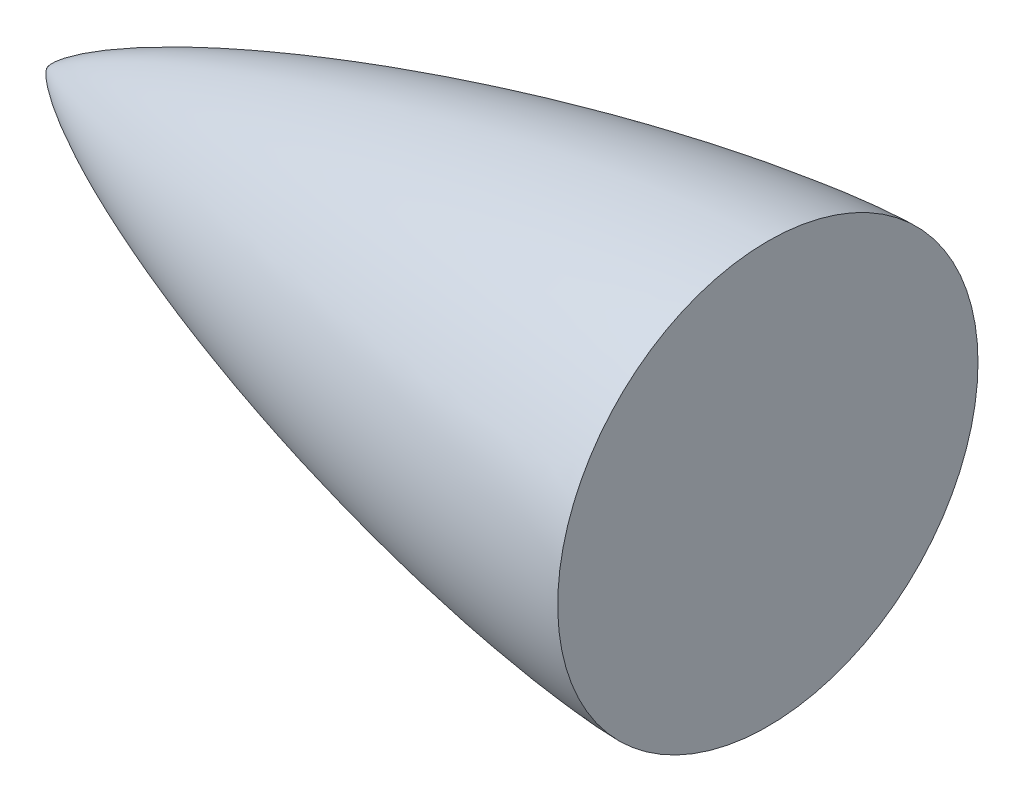
SolidWorks part; units mm, degrees
ref_plane "Front Plane" through (0, 0, 0) normal (0, 0, 1) x (1, 0, 0)
ref_plane "Top Plane" through (0, 0, 0) normal (0, 1, 0) x (1, 0, 0)
ref_plane "Right Plane" through (0, 0, 0) normal (1, 0, 0) x (0, 0, -1)
sketch "Sketch1" plane through (0, 0, 0) normal (0, 0, 1) x (1, 0, 0)
  line L0 (0, 0) -> (304.8, 0) construction
  line L1 (0, 0) -> (0, 88.9) construction
  line L2 (304.8, 88.9151) -> (304.8, 0)
  line L3 (304.8, 0) -> (0, 0)
  spline S0 degree 4 poles (0, 0) (0.0015, 0.0119) (0.0057, 0.0356) (0.0182, 0.0821) (0.05, 0.1729) (0.0937, 0.2728) (0.1482, 0.3816) (0.2338, 0.5371) (0.3732, 0.766) (0.6385, 1.1485) (1.1395, 1.7727) (2.0247, 2.7262) (3.5433, 4.142) (6.1054, 6.2185) (10.3073, 9.1835) (16.4637, 12.9823) (26.3502, 18.3873) (39.6719, 24.7722) (55.7804, 31.646) (74.2558, 38.7324) (92.9294, 45.2746) (111.76, 51.3489) (130.7203, 57.0039) (149.7928, 62.2678) (168.9648, 67.1561) (188.2278, 71.673) (207.5755, 75.8125) (227.0037, 79.5561) (246.5101, 82.8706) (263.6459, 85.3431) (278.3826, 87.091) (289.376, 88.1032) (296.0263, 88.5742) (300.7874, 88.8121) (303.0799, 88.8877) (304.2266, 88.912) (304.8, 88.9151) knots 0 0 0 0 0 0.00015 0.000299 0.000599 0.001198 0.001506 0.001815 0.002809 0.004534 0.0073 0.011775 0.018999 0.03037 0.048342 0.07578 0.109043 0.170642 0.232242 0.293841 0.35544 0.41704 0.478639 0.540238 0.601837 0.663437 0.725036 0.786635 0.848235 0.909834 0.940634 0.971433 0.985717 0.992858 1 1 1 1 1 construction
  spline S1 degree 4 poles (0, 0) (0.0015, 0.0119) (0.0057, 0.0356) (0.0182, 0.0821) (0.05, 0.1729) (0.0937, 0.2728) (0.1482, 0.3816) (0.2338, 0.5371) (0.3732, 0.766) (0.6385, 1.1485) (1.1395, 1.7727) (2.0247, 2.7262) (3.5433, 4.142) (6.1054, 6.2185) (10.3073, 9.1835) (16.4637, 12.9823) (26.3502, 18.3873) (39.6719, 24.7722) (55.7804, 31.646) (74.2558, 38.7324) (92.9294, 45.2746) (111.76, 51.3489) (130.7203, 57.0039) (149.7928, 62.2678) (168.9648, 67.1561) (188.2278, 71.673) (207.5755, 75.8125) (227.0037, 79.5561) (246.5101, 82.8706) (263.6459, 85.3431) (278.3826, 87.091) (289.376, 88.1032) (296.0263, 88.5742) (300.7874, 88.8121) (303.0799, 88.8877) (304.2266, 88.912) (304.8, 88.9151) knots 0 0 0 0 0 0.00015 0.000299 0.000599 0.001198 0.001506 0.001815 0.002809 0.004534 0.0073 0.011775 0.018999 0.03037 0.048342 0.07578 0.109043 0.170642 0.232242 0.293841 0.35544 0.41704 0.478639 0.540238 0.601837 0.663437 0.725036 0.786635 0.848235 0.909834 0.940634 0.971433 0.985717 0.992858 1 1 1 1 1
  dimension "D1" = 304.8
  dimension "D2" = 88.9
revolve "Revolve1" add sketch "Sketch1" angle 360 about L3
